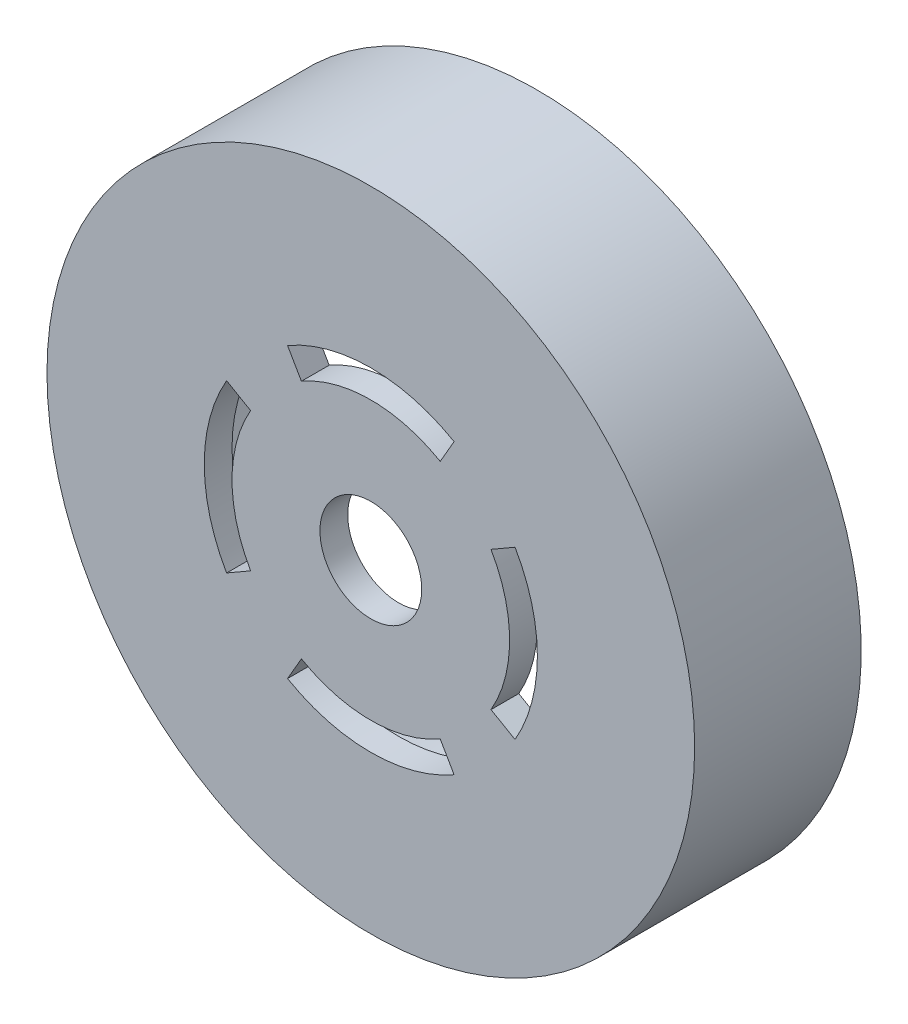
SolidWorks part; units mm, degrees
ref_plane "前视基准面" through (0, 0, 0) normal (0, 0, 1) x (1, 0, 0)
ref_plane "上视基准面" through (0, 0, 0) normal (0, 1, 0) x (1, 0, 0)
ref_plane "右视基准面" through (0, 0, 0) normal (1, 0, 0) x (0, 0, -1)
other "Configuration Table"
sketch "草图2" plane through (0, 0, 0) normal (0, 0, 1) x (1, 0, 0)
  circle A0 centre (0, 0) radius 35
  circle A1 centre (0, 0) radius 5.5
  dimension "D1" = 70
  dimension "D2" = 11
extrude "凸台-拉伸1" add sketch "草图2" along normal blind 5
sketch "草图3" plane through (0, 0, 0) normal (0, 0, -1) x (-1, 0, 0)
  circle A0 centre (0, 0) radius 30.1
  circle A1 centre (0, 0) radius 35
  dimension "D1" = 60.2
extrude "凸台-拉伸2" add sketch "草图3" along normal blind 15
sketch "草图4" plane through (0, 0, -15) normal (0, 0, -1) x (-1, 0, 0)
  line L0 (0, 0) -> (0, 32.5)
  line L1 (0, 0) -> (32.5, 0)
  line L2 (0, 0) -> (0, -32.5)
  line L3 (0, 0) -> (-32.5, 0)
  circle A0 centre (0, 32.5) radius 1.55
  circle A1 centre (32.5, 0) radius 1.55
  circle A2 centre (0, -32.5) radius 1.55
  circle A3 centre (-32.5, 0) radius 1.55
  point P9 (0, 0)
  point P17 (0, 0)
  dimension "D2" = 4
  dimension "D1" = 4
extrude "切除-拉伸1" cut sketch "草图4" against normal blind 10 contours A0 | A1 | A2 | A3 region at (1.065, 33.565, -15) region at (-32.5, 1.5062, -15) region at (-1.065, -31.435, -15) region at (34.0062, 0, -15)
sketch "草图9" plane through (0, 0, -15) normal (0, 0, -1) x (-1, 0, 0)
  line L0 (0, 0) -> (0, 32.5) construction
  line L1 (0, 0) -> (-21.2839, 21.2839) construction
  circle A0 centre (0, 0) radius 30.1 construction
  arc A1 (-22.0133, 20.5286) -> (-20.5286, 22.0133) centre (-21.2839, 21.2839) cw
  arc A2 (20.5286, 22.0133) -> (22.0133, 20.5286) centre (21.2839, 21.2839) cw
  arc A3 (22.0133, -20.5286) -> (20.5286, -22.0133) centre (21.2839, -21.2839) cw
  arc A4 (-20.5286, -22.0133) -> (-22.0133, -20.5286) centre (-21.2839, -21.2839) cw
  arc A5 (-20.5286, 22.0133) -> (-22.0133, 20.5286) centre (0, 0) ccw
  arc A6 (-22.0133, -20.5286) -> (-20.5286, -22.0133) centre (0, 0) ccw
  arc A7 (20.5286, -22.0133) -> (22.0133, -20.5286) centre (0, 0) ccw
  arc A8 (22.0133, 20.5286) -> (20.5286, 22.0133) centre (0, 0) ccw
  point P21 (0, 0)
  dimension "D2" = 1.05
  dimension "D1" = 45
  dimension "D3" = 4
extrude "切除-拉伸5" cut sketch "草图9" against normal up to surface (15 mm away) up to face at (5.5, 0, 0)
fillet "圆角1" radius 1 4 edges at (0, -30.1, -15) (-30.1, 0, -15) (0, 30.1, -15) (30.1, 0, -15)
sketch "草图10" plane through (0, 0, 5) normal (0, 0, 1) x (1, 0, 0)
  circle A0 centre (0, 0) radius 35
extrude "切除-拉伸6" cut sketch "草图10" against normal blind 2
sketch "草图11" plane through (0, 0, 0) normal (0, 0, -1) x (-1, 0, 0)
  line L0 (0, 0) -> (0, 32.5) construction
  line L1 (0, 0) -> (32.5, 0) construction
  line L2 (12.9904, 7.5) -> (15.5885, 9)
  line L3 (-7.5, 12.9904) -> (-9, 15.5885)
  line L4 (7.5, 12.9904) -> (9, 15.5885)
  line L5 (12.9904, -7.5) -> (15.5885, -9)
  line L6 (0, 0) -> (0, -32.5) construction
  line L7 (7.5, -12.9904) -> (9, -15.5885)
  line L8 (-7.5, -12.9904) -> (-9, -15.5885)
  line L9 (0, 0) -> (-32.5, 0) construction
  line L10 (-12.9904, -7.5) -> (-15.5885, -9)
  line L11 (-12.9904, 7.5) -> (-15.5885, 9)
  arc A1 (7.5, 12.9904) -> (-7.5, 12.9904) centre (0, 0) ccw
  arc A2 (9, 15.5885) -> (-9, 15.5885) centre (0, 0) ccw
  arc A3 (12.9904, -7.5) -> (12.9904, 7.5) centre (0, 0) ccw
  arc A4 (15.5885, -9) -> (15.5885, 9) centre (0, 0) ccw
  arc A5 (-7.5, -12.9904) -> (7.5, -12.9904) centre (0, 0) ccw
  arc A6 (-9, -15.5885) -> (9, -15.5885) centre (0, 0) ccw
  arc A7 (-12.9904, 7.5) -> (-12.9904, -7.5) centre (0, 0) ccw
  arc A8 (-15.5885, 9) -> (-15.5885, -9) centre (0, 0) ccw
  point P26 (0, 0)
  dimension "D4" = 30
  dimension "D1" = 4
extrude "切除-拉伸7" cut sketch "草图11" against normal blind 10
